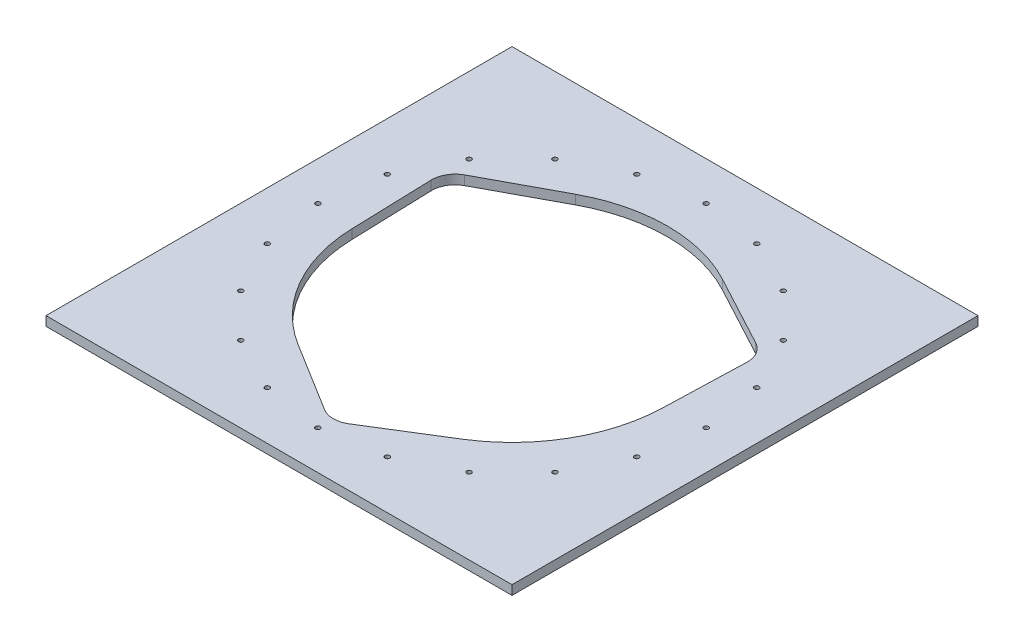
SolidWorks part; units mm, degrees
ref_plane "Front Plane" through (0, 0, 0) normal (0, 0, 1) x (1, 0, 0)
ref_plane "Top Plane" through (0, 0, 0) normal (0, 1, 0) x (1, 0, 0)
ref_plane "Right Plane" through (0, 0, 0) normal (1, 0, 0) x (0, 0, -1)
sketch "Sketch1" plane through (0, 0, 0) normal (0, 1, 0) x (1, 0, 0)
  line L0 (-203.1905, 99.0638) -> (-199.9026, -6.2414)
  line L1 (-300, 300) -> (300, 300)
  line L2 (-300, 300) -> (-300, -300)
  line L3 (-300, -300) -> (300, -300)
  line L4 (300, 300) -> (300, -300)
  line L5 (-187.387, 126.4362) -> (-94.546, 176.2414)
  line L6 (15.8035, -225.5) -> (105.3565, -170)
  line L7 (-15.8035, -225.5) -> (-105.3565, -170)
  line L8 (187.387, 126.4362) -> (94.546, 176.2414)
  line L9 (203.1905, 99.0638) -> (199.9026, -6.2414)
  arc A0 (105.3565, -170) -> (199.9026, -6.2414) centre (0, 0) ccw
  arc A1 (-15.8035, -225.5) -> (15.8035, -225.5) centre (0, -200) ccw
  arc A2 (-187.387, 126.4362) -> (-203.1905, 99.0638) centre (-173.2051, 100) ccw
  arc A3 (203.1905, 99.0638) -> (187.387, 126.4362) centre (173.2051, 100) ccw
  arc A4 (-199.9026, -6.2414) -> (-105.3565, -170) centre (0, 0) ccw
  arc A5 (94.546, 176.2414) -> (-94.546, 176.2414) centre (0, 0) ccw
  circle A6 centre (0, 250) radius 3
  circle A7 centre (77.2542, 237.7641) radius 3
  circle A8 centre (146.9463, 202.2542) radius 3
  circle A9 centre (202.2542, 146.9463) radius 3
  circle A10 centre (237.7641, 77.2542) radius 3
  circle A11 centre (250, 0) radius 3
  circle A12 centre (237.7641, -77.2542) radius 3
  circle A13 centre (202.2542, -146.9463) radius 3
  circle A14 centre (146.9463, -202.2542) radius 3
  circle A15 centre (77.2542, -237.7641) radius 3
  circle A16 centre (0, -250) radius 3
  circle A17 centre (-77.2542, -237.7641) radius 3
  circle A18 centre (-146.9463, -202.2542) radius 3
  circle A19 centre (-202.2542, -146.9463) radius 3
  circle A20 centre (-237.7641, -77.2542) radius 3
  circle A21 centre (-250, 0) radius 3
  circle A22 centre (-237.7641, 77.2542) radius 3
  circle A23 centre (-202.2542, 146.9463) radius 3
  circle A24 centre (-146.9463, 202.2542) radius 3
  circle A25 centre (-77.2542, 237.7641) radius 3
  circle A26 centre (0, 50) radius 3
  circle A27 centre (43.3013, 25) radius 3
  circle A28 centre (43.3013, -25) radius 3
  circle A29 centre (0, -50) radius 3
  circle A30 centre (-43.3013, -25) radius 3
  circle A31 centre (-43.3013, 25) radius 3
  point P7 (-300, 0)
  point P8 (0, -300)
  point P26 (0, 0)
  point P67 (0, 0)
  point P79 (0, 0)
  dimension "D3" = 400
  dimension "D4" = 60
  dimension "D6" = 250
  dimension "D7" = 6
  dimension "D10" = 6
  dimension "D1" = 600
  dimension "D2" = 600
  dimension "D9" = 50
  dimension "D5" = 3
  dimension "D8" = 20
  dimension "D11" = 6
extrude "Boss-Extrude1" add sketch "Sketch1" along normal blind 12 contours L4 L1 L2 L3 A25 A24 A23 A22 A21 A20 A19 A18 A17 A16 A15 A14 A13 A12 A11 A10 A9 A8 A7 A6 A5 L8 A3 L9 A0 L6 region at (0, 0, -291.5147)
